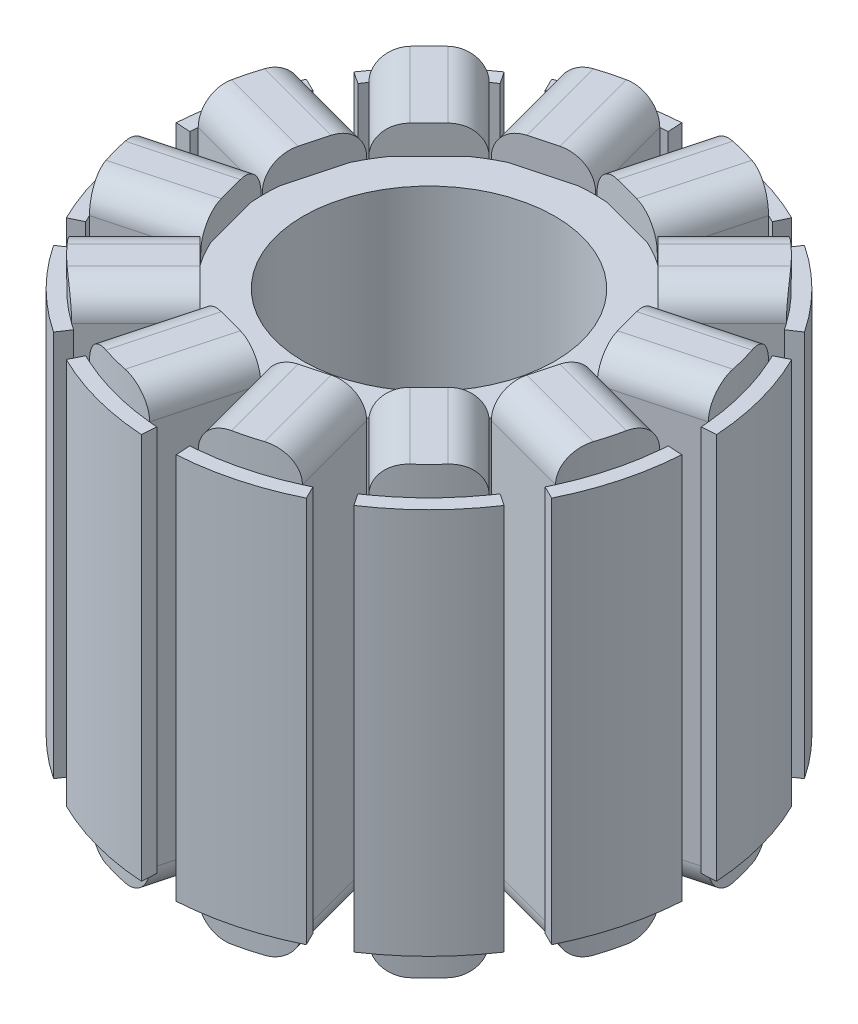
SolidWorks part; units mm, degrees
material "Plain Carbon Steel"
ref_plane "Front Plane" through (0, 0, 0) normal (0, 0, 1) x (1, 0, 0)
ref_plane "Top Plane" through (0, 0, 0) normal (0, 1, 0) x (1, 0, 0)
ref_plane "Right Plane" through (0, 0, 0) normal (1, 0, 0) x (0, 0, -1)
sketch "Sketch1" plane through (0, 0, 0) normal (0, 1, 0) x (1, 0, 0)
  circle A0 centre (0, 0) radius 14
  circle A1 centre (0, 0) radius 6.5
  dimension "D1" = 28
  dimension "D2" = 13
extrude "Stator Base" add sketch "Sketch1" along normal mid plane 20
sketch "Sketch2" plane through (0, 10, 0) normal (0, 1, 0) x (1, 0, 0)
  line L0 (0.9, 13.971) -> (0.8518, 13.2226)
  line L1 (-0.9, 13.971) -> (-0.8518, 13.2226)
  line L2 (-1.9584, 13.1045) -> (-0.7165, 8.4697)
  line L3 (0.7165, 8.4697) -> (1.9584, 13.1045)
  line L4 (0, 0) -> (3.6235, 13.523) construction
  line L5 (0, 0) -> (-3.6235, 13.523) construction
  line L6 (0, 0) -> (0, 6.5) construction
  line L7 (0.9, 13.971) -> (3.6235, 13.523) construction
  line L8 (1.9584, 13.1045) -> (3.4073, 12.7162) construction
  line L9 (-0.9, 13.971) -> (-3.6235, 13.523) construction
  line L10 (-1.9584, 13.1045) -> (-3.4073, 12.7162) construction
  arc A0 (-0.9, 13.971) -> (0.9, 13.971) centre (0, 0) cw
  circle A1 centre (0, 0) radius 14 construction
  arc A4 (-0.7165, 8.4697) -> (0.7165, 8.4697) centre (0, 0) cw
  circle A5 centre (0, 0) radius 6.5 construction
  arc A7 (-1.9584, 13.1045) -> (-0.8518, 13.2226) centre (0, 0) cw
  arc A8 (0.8518, 13.2226) -> (1.9584, 13.1045) centre (0, 0) cw
  dimension "D4" = 8.5
  dimension "D1" = 15
  dimension "D2" = 30
  dimension "D3" = 0.75
  dimension "D5" = 1.8
  dimension "D6" = 3
extrude "Stator Profile" cut sketch "Sketch2" against normal through all
pattern_circular "Profile Pattern" count 12 over 360 about axis through (0, 10, 0) along (0, -1, 0) of "Stator Profile"
ref_plane "Plane1" through (6.9767, 10, 4.8554) normal (0.7071, 0, 0.7071) x (0.7071, 0, -0.7071)
sketch "Sketch3" plane through (6.9767, 10, 4.8554) normal (0.7071, 0, 0.7071) x (0.7071, 0, -0.7071)
  line L0 (-3, -20) -> (-3, 0)
  line L1 (-3, -20) -> (-3, 0)
  line L2 (0, -20) -> (0, 0)
  line L3 (0, -20) -> (0, 0)
  line L4 (-3, 0) -> (0, 0)
  line L5 (-3, -20) -> (0, -20)
  line L6 (-1.5, 1.5) -> (-1.5, 0) construction
  line L7 (-3.7, 1.5) -> (0.7, 1.5)
  line L8 (-3.7, 1.5) -> (-3.7, -21.5)
  line L9 (-3.7, -21.5) -> (0.7, -21.5)
  line L10 (0.7, 1.5) -> (0.7, -21.5)
  line L11 (0.7, -10) -> (0, -10) construction
  dimension "D1" = 23
  dimension "D2" = 4.4
extrude "Winding" add sketch "Sketch3" along normal up to surface (4.7982 mm away) up to face at (7.8021, 0, 10.7021)
fillet "Winding Fillet" radius 1.5 4 edges at (6.022, -11.5, 9.1332) (9.1332, -11.5, 6.022) (9.1332, 11.5, 6.022) (6.022, 11.5, 9.1332)
pattern_circular "CirPattern3" count 12 over 360 about axis through (0, 10, 0) along (0, -1, 0) of "Winding", "Winding Fillet"
equation "\"D2@Sketch2\"=360/12"
